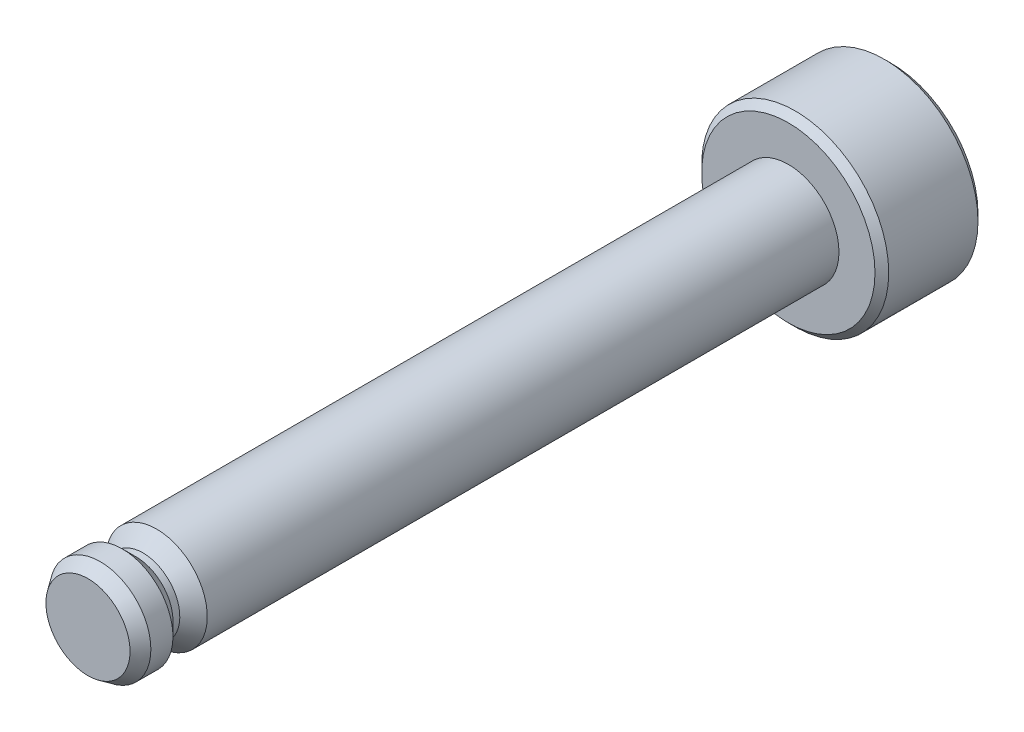
SolidWorks part; units mm, degrees
ref_plane "Front" through (0, 0, 0) normal (0, 0, 1) x (1, 0, 0)
ref_plane "Top" through (0, 0, 0) normal (0, 1, 0) x (1, 0, 0)
ref_plane "Right" through (0, 0, 0) normal (1, 0, 0) x (0, 0, -1)
sketch "Sketch2" plane through (0, 0, 0) normal (0, 0, 1) x (1, 0, 0)
  circle A0 centre (0, 0) radius 1.475
  dimension "D1" = 2.95
extrude "Shaft" add sketch "Sketch2" along normal blind 20.4
sketch "Sketch5" plane through (0, 0, 0) normal (0, 0, 1) x (1, 0, 0)
  circle A0 centre (0, 0) radius 2.725
  dimension "D1" = 5.45
extrude "Head" add sketch "Sketch5" against normal blind 3
chamfer "Chamfer1" distance 0.25 angle 55 1 edges at (1.475, 0, 20.4) first distance on face at (1.475, 0, 20.4)
chamfer "Deburs" distance 0.2 angle 45 2 edges at (2.725, 0, 0) (2.725, 0, -3)
sketch "Sketch6" plane through (0, 0, 0) normal (1, 0, 0) x (0, 0, -1)
  line L0 (0, 0) -> (-18.9, 0) construction
  line L1 (-18.9, 0) -> (-18.9, 1.075) construction
  line L2 (0, 1.475) -> (-20.043, 1.475) construction
  line L3 (-19.4, 1.475) -> (-18.4, 1.475)
  line L4 (-18.4, 1.475) -> (-18.8, 1.075)
  line L5 (-18.8, 1.075) -> (-19, 1.075)
  line L6 (-19, 1.075) -> (-19.4, 1.475)
  line L7 (-18.9, 1.075) -> (-18.9, 1.475) construction
  dimension "D1" = 18.9
  dimension "D2" = 0.4
  dimension "D3" = 1
revolve "e-Clip Notch Long" cut sketch "Sketch6" angle 360 about L0
equation "\"D1@Sketch2\"=\"Plastic Hardware OD@Box Assy.Assembly\""
equation "\"D1\"= \"Countersink Diameter@Box Assy.Assembly\" - .3mm"
equation "\"D1@Head\"=\"Countersink Depth@Box Assy.Assembly\""
equation "\"Length\"= 20mm"
equation "\"D1@Shaft\"=\"Length\"+.4mm"
equation "\"D1@Sketch6\"=\"Length\"-1.1mm"
